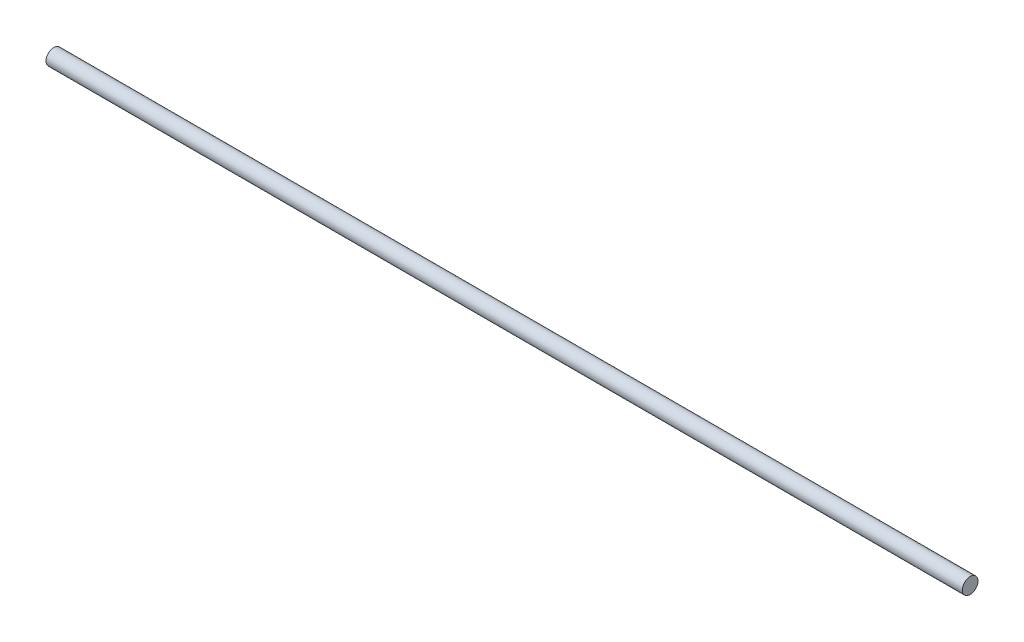
SolidWorks part; units mm, degrees
ref_plane "Plan de face" through (0, 0, 0) normal (0, 0, 1) x (1, 0, 0)
ref_plane "Plan de dessus" through (0, 0, 0) normal (0, 1, 0) x (1, 0, 0)
ref_plane "Plan de droite" through (0, 0, 0) normal (1, 0, 0) x (0, 0, -1)
sketch "Esquisse1" plane through (0, 0, 0) normal (1, 0, 0) x (0, 0, -1)
  circle A0 centre (0, 0) radius 2.5
  dimension "D1" = 5
extrude "Boss.-Extru.1" add sketch "Esquisse1" along normal blind 292
sketch "Esquisse3" plane through (0, 0, 0) normal (-1, 0, 0) x (0, 0, 1)
  circle A0 centre (0, 0) radius 2.6082
  dimension "D1" = 5.2165
curve "Hélice/Spirale1" pitch 0.5 height 292.5 turns 585
sketch "Esquisse6" plane through (0, 0, 0) normal (0, 0, 1) x (1, 0, 0)
  line L0 (0.2031, 2.1482) -> (-3.4223, 8.4277) construction
  line L1 (0, 2.5) -> (0.1562, 2.2294)
  line L2 (0.2031, 2.1482) -> (0.2031, 2.2294) construction
  line L3 (0.2031, 2.1482) -> (0.4531, 2.5812) construction
  line L4 (0, 2.5) -> (0, 2.5812)
  line L5 (0.25, 2.2294) -> (0.1562, 2.2294)
  line L6 (0.25, 2.2294) -> (0.4062, 2.5)
  line L7 (0, 2.5812) -> (0.4531, 2.5812)
  line L8 (0.4531, 2.5812) -> (0.5, 2.5)
  line L9 (0.4062, 2.5) -> (0.5, 2.5)
  line L10 (0, 2.5) -> (0, -2.5) construction
  line L11 (0.25, 2.2294) -> (0.2031, 2.1482) construction
  dimension "ANGLE" = 60
  dimension "ANGLE2" = 60
  dimension "D1" = 2.5
  dimension "D2" = 2.2294
  dimension "D3" = 0.433
sweep "Enlèvement de matière-Balayage1" [suppressed] cut profiles "Esquisse6" path "Hélice/Spirale1"
equation "\"D5@Esquisse6\" = \"D4@Esquisse6\" / 2"
equation "\"D2@Esquisse6\" = ( \"diametre_mm\" - ( 1.0825 * \"pas_mm\" ) ) / 2"
equation "\"ANGLE2@Esquisse6\" = \"ANGLE@Esquisse6\""
equation "\"D1@Esquisse6\"=\"diametre_mm\"/2"
equation "\"D1@Esquisse1\"=\"diametre_mm\""
equation "\"D1@Esquisse3\"=\"diametre_mm\"+(0.866*\"pas_mm\")/2"
equation "\"D4@Hélice/Spirale1\"=\"pas_mm\""
equation "\"D3@Hélice/Spirale1\"=\"longueur_mm\"+\"pas_mm\""
equation "\"D1@Boss.-Extru.1\"=\"longueur_mm\""
equation "\"D3@Esquisse6\"=\"pas_mm\"*0.866"
